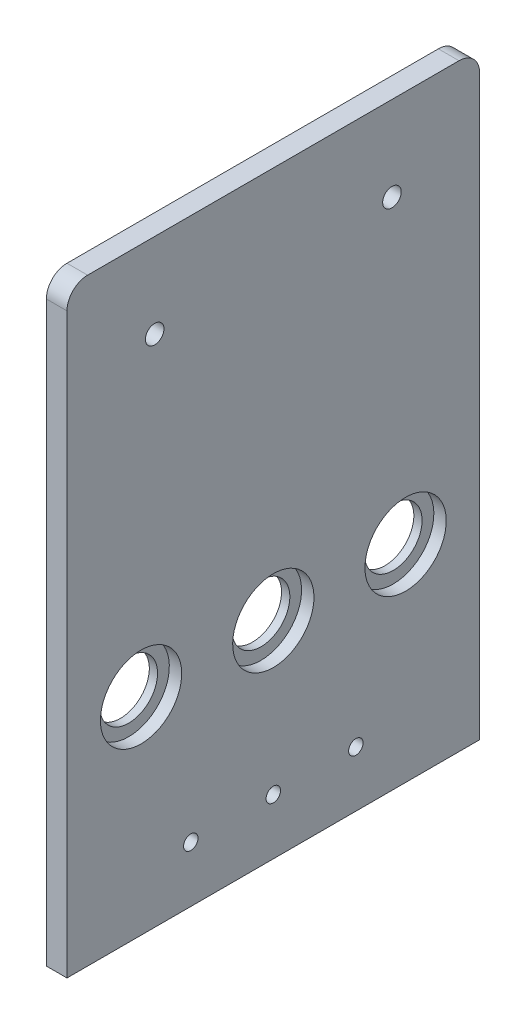
SolidWorks part; units mm, degrees
note: The reader was unsure of these and kept them because the rebuilt part matched: shared geometry of "Sketch4<4>", "Sketch4<6>".
ref_plane "Ön Düzlem" through (0, 0, 0) normal (0, 0, 1) x (1, 0, 0)
ref_plane "Üst Düzlem" through (0, 0, 0) normal (0, 1, 0) x (1, 0, 0)
ref_plane "Sağ Düzlem" through (0, 0, 0) normal (1, 0, 0) x (0, 0, -1)
sketch "Sketch1" plane through (0, 0, 0) normal (0, 0, 1) x (1, 0, 0)
  line L1 (-15.6006, 140) -> (-10.6006, 140)
  line L2 (-15.6006, 140) -> (-15.6006, 0)
  line L3 (-15.6006, 0) -> (-10.6006, 0)
  line L4 (-10.6006, 140) -> (-10.6006, 0)
  line L5 (-15.6006, 140) -> (-10.6006, 0) construction
  line L6 (-15.6006, 0) -> (-10.6006, 140) construction
  line L7 (-15.6006, 0) -> (94.3994, 0)
  line L8 (-15.6006, 0) -> (-15.6006, -5)
  line L9 (-15.6006, -5) -> (94.3994, -5)
  line L10 (94.3994, 0) -> (94.3994, -5)
  line L11 (94.3994, 0) -> (89.3994, 0)
  line L12 (94.3994, 0) -> (94.3994, 140)
  line L13 (94.3994, 140) -> (89.3994, 140)
  line L14 (89.3994, 0) -> (89.3994, 140)
  point P0 (-13.1006, 70)
  dimension "D1" = 5
  dimension "D2" = 140
  dimension "D3" = 5
  dimension "D4" = 110
  dimension "D5" = 5
extrude "Boss-Extrude1" add sketch "Sketch1" against normal blind 100 contours L10 L7 L3 L8 L9 | L14 L7 L12 L13
sketch "Sketch4" plane through (89.3994, 0, 0) normal (-1, 0, 0) x (0, 0, 1)
  line L0 (0, 0) -> (0, 45)
  line L1 (0, 0) -> (0, 140) construction
  line L2 (0, 45) -> (-100, 45)
  line L3 (-100, 0) -> (-100, 140) construction
  line L4 (-50, 45) -> (-82.05, 45)
  line L5 (-50, 45) -> (-17.95, 45)
  circle A0 centre (-50, 45) radius 9.85
  circle A1 centre (-82.05, 45) radius 9.85
  circle A2 centre (-17.95, 45) radius 9.85
  circle A3 centre (-82.05, 45) radius 7
  circle A4 centre (-50, 45) radius 7
  circle A5 centre (-17.95, 45) radius 7
  dimension "D4" = 19.7
  dimension "D5" = 19.7
  dimension "D6" = 19.7
  dimension "D7" = 14
  dimension "D8" = 14
  dimension "D9" = 14
  dimension "D1" = 45
  dimension "D2" = 32.05
  dimension "D3" = 32.05
extrude "Cut-Extrude3" cut sketch "Sketch4" along normal through all both and the other way through all contours L2 A3 L4 | L4 A3 L2 | L2 A4 | L2 A4 | L2 A5 | L2 A5
extrude "Cut-Extrude4" cut sketch "Sketch4<4>" against normal blind 3
sketch "Sketch4<4>" plane through (89.3994, 0, 0) normal (-1, 0, 0) x (0, 0, 1) same geometry as "Sketch4"
extrude "Cut-Extrude5" cut sketch "Sketch4<6>" along normal blind 103
sketch "Sketch4<6>" plane through (89.3994, 0, 0) normal (-1, 0, 0) x (0, 0, 1) same geometry as "Sketch4"
sketch "Sketch5" plane through (-15.6006, 0, 0) normal (-1, 0, 0) x (0, 0, 1)
  line L0 (0, 140) -> (0, 119.5)
  line L1 (0, 140) -> (0, -5) construction
  line L2 (0, 119.5) -> (-21.25, 119.5)
  line L3 (-100, 140) -> (-100, 119.5)
  line L4 (-100, 140) -> (-100, -5) construction
  line L5 (-100, 119.5) -> (-78.75, 119.5)
  circle A0 centre (-78.75, 119.5) radius 2.25
  circle A1 centre (-21.25, 119.5) radius 2.25
  dimension "D4" = 4.5
  dimension "D5" = 4.5
  dimension "D1" = 20.5
  dimension "D2" = 21.25
  dimension "D3" = 21.25
extrude "Cut-Extrude6" cut sketch "Sketch5" against normal up to next and the other way through all
sketch "Sketch6" plane through (0, -5, 0) normal (0, -1, 0) x (1, 0, 0)
  line L0 (39.3994, -50) -> (71.8994, -50)
  line L1 (39.3994, -50) -> (6.8994, -50)
  circle A0 centre (71.8994, -50) radius 2.25
  circle A1 centre (6.8994, -50) radius 2.25
  dimension "D3" = 4.5
  dimension "D4" = 4.5
  dimension "D1" = 32.5
  dimension "D2" = 32.5
extrude "Cut-Extrude7" cut sketch "Sketch6" against normal up to next
sketch "Sketch7" plane through (0, 0, 0) normal (0, 1, 0) x (1, 0, 0)
  line L0 (39.3994, 100) -> (33.3994, 100)
  line L1 (-10.6006, 100) -> (89.3994, 100) construction
  line L2 (33.3994, 100) -> (45.3994, 100)
  line L3 (9.1494, 50) -> (69.6494, 50)
  line L4 (33.3994, 100) -> (45.3994, 100)
  line L5 (33.3994, 100) -> (33.3994, 85)
  line L6 (33.3994, 85) -> (45.3994, 85)
  line L7 (45.3994, 100) -> (45.3994, 85)
  line L8 (33.3994, 0) -> (45.3994, 0)
  line L9 (33.3994, 15) -> (45.3994, 15)
  line L10 (45.3994, 0) -> (45.3994, 15)
  line L11 (33.3994, 0) -> (33.3994, 15)
  circle A0 centre (6.8994, 50) radius 2.25 construction
  circle A1 centre (71.8994, 50) radius 2.25 construction
  line M10 (-10.6006, 0) -> (89.3994, 0)
  line M12 (89.3994, 100) -> (-10.6006, 100)
  dimension "D1" = 6
  dimension "D2" = 12
  dimension "D3" = 15
extrude "Cut-Extrude8" cut sketch "Sketch7" against normal through all contours L7 L5 L6 M12 | L11 L10 L9 M10
fillet "Fillet3" radius 2.5 10 edges at (45.3994, -2.5, -15) (45.3994, -2.5, 0) (45.3994, -5, -7.5) (45.3994, 0, -7.5) (39.3994, -5, -15) (39.3994, 0, -15) (33.3994, -5, -7.5) (33.3994, -2.5, 0) (33.3994, -2.5, -15) (33.3994, 0, -7.5)
fillet "Fillet4" radius 2.5 10 edges at (33.3994, -2.5, -85) (33.3994, -2.5, -100) (33.3994, -5, -92.5) (33.3994, 0, -92.5) (39.3994, -5, -85) (39.3994, 0, -85) (45.3994, -5, -92.5) (45.3994, -2.5, -100) (45.3994, -2.5, -85) (45.3994, 0, -92.5)
fillet "Fillet6" radius 5 4 edges at (-13.1006, 140, 0) (-13.1006, 140, -100) (91.8994, 140, 0) (91.8994, 140, -100)
sketch "Sketch8" plane through (0, 0, 0) normal (0, 0, 1) x (1, 0, 0)
  line L1 (-15.6006, -5) -> (-10.6006, -5)
  line L2 (-15.6006, -5) -> (-15.6006, 140)
  line L3 (-15.6006, 140) -> (-10.6006, 140)
  line L4 (-10.6006, -5) -> (-10.6006, 140)
  line L5 (-10.6006, -5) -> (94.3994, -5)
  line L6 (-10.6006, -5) -> (-10.6006, 140)
  line L7 (-10.6006, 140) -> (94.3994, 140)
  line L8 (94.3994, -5) -> (94.3994, 140)
  line M1 (-10.6006, 0) -> (-10.6006, 135)
  line M4 (-15.6006, -5) -> (30.8994, -5)
  line M5 (30.8994, -5) -> (30.8994, 0)
  line M6 (30.8994, 0) -> (-10.6006, 0)
extrude "Cut-Extrude11" cut sketch "Sketch8" against normal up to next contours L4 M4 M5 M6 | L5 L8 L7 L4 M1 M6 M5
sketch "Sketch9" plane through (-10.6006, 0, 0) normal (1, 0, 0) x (0, 0, -1)
  line L0 (50, -5) -> (50, 8.5)
  line L1 (100, -5) -> (0, -5) construction
  circle A0 centre (50, 8.5) radius 1.75
  circle A1 centre (70, 8.5) radius 1.75
  circle A2 centre (50, 8.5) radius 1.75
  circle A3 centre (30, 8.5) radius 1.75
  dimension "D2" = 3.5
  dimension "D1" = 13.5
  dimension "D3" = 2
  dimension "D4" = 2
extrude "Cut-Extrude12" cut sketch "Sketch9" against normal up to next
